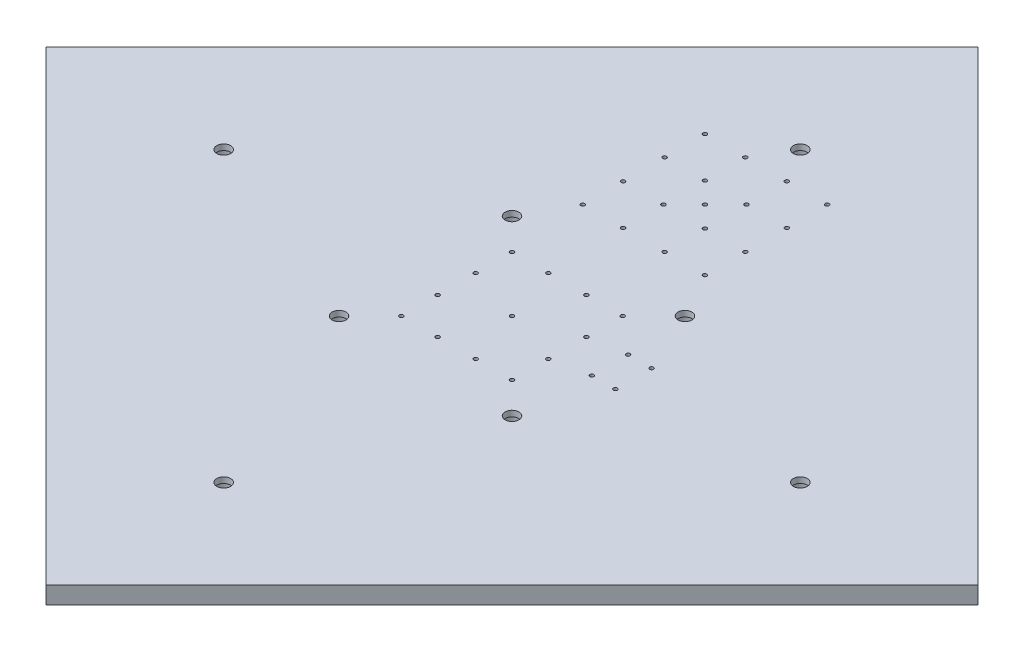
SolidWorks part; units mm, degrees
ref_plane "Front Plane" through (0, 0, 0) normal (0, 0, 1) x (1, 0, 0)
ref_plane "Top Plane" through (0, 0, 0) normal (0, 1, 0) x (1, 0, 0)
ref_plane "Right Plane" through (0, 0, 0) normal (1, 0, 0) x (0, 0, -1)
sketch "Sketch1" plane through (0, 0, 0) normal (0, 1, 0) x (1, 0, 0)
  line L0 (-404.1115, 0) -> (0, 404.1115)
  line L5 (-404.1115, 0) -> (0, -404.1115)
  line L6 (0, 404.1115) -> (404.1115, 0)
  line L7 (0, -404.1115) -> (404.1115, 0)
  line L8 (-404.1115, 0) -> (404.1115, 0) construction
  line L9 (0, 404.1115) -> (0, -404.1115) construction
  point P1 (0, 0)
  dimension "D1" = 571.5
extrude "Boss-Extrude1" add sketch "Sketch1" along normal blind 15
sketch "Extrusion Hole locations" plane through (0, 0, 0) normal (0, 1, 0) x (1, 0, 0)
  line L1 (75, -75) -> (-75, -75) construction
  line L2 (75, -75) -> (75, 75) construction
  line L3 (75, 75) -> (-75, 75) construction
  line L4 (-75, -75) -> (-75, 75) construction
  line L5 (75, -75) -> (-75, 75) construction
  line L6 (75, 75) -> (-75, -75) construction
  point P3 (0, 250)
  point P14 (250, 0)
  point P15 (0, -250)
  point P16 (-250, 0)
  point P105 (75, 75)
  point P108 (-75, 75)
  point P111 (-75, -75)
  point P114 (75, -75)
  dimension "D1" = 150
  dimension "D2" = 250
  dimension "D4" = 4
hole_wizard "CBORE for M10 SHCS1" positions "Extrusion Hole locations" profile "Sketch3" counterbore size "M10" standard "ANSI Metric" end condition through all
sketch "Sketch3" plane through (75, 0, 75) normal (1, 0, 0) x (0, 0, -1)
  line L0 (0, 0) -> (0, 15)
  line L1 (0, 15) -> (6, 15)
  line L3 (6, 15) -> (6, 10)
  line L4 (6, 10) -> (9, 10)
  line L5 (9, 10) -> (9, 0)
  line L7 (9, 0) -> (0, 0)
  line L11 (0, -6.35) -> (0, 107.95) construction
  dimension "Thru Hole Dia." = 12
  dimension "Thru Hole Depth" = 15
  dimension "C'Bore Dia." = 18
  dimension "C'Bore Depth" = 10
hole_wizard "CBORE for M3 SHCS1" positions "Sketch6" profile "Sketch7" counterbore size "M3" standard "ANSI Metric"
sketch "Sketch6" plane through (0, 0, 0) normal (0, -1, 0) x (-1, 0, 0)
  point P0 (0, 0)
  point P1 (0, 0)
  point P2 (-48, -48)
  point P3 (-48, -48)
  point P4 (16.5, -48)
  point P5 (-16.5, -48)
  point P6 (-16.5, -48)
  point P7 (48, -48)
  point P8 (48, -16.5)
  point P9 (48, 16.5)
  point P10 (48, 48)
  point P11 (16.5, 48)
  point P12 (-16.5, 48)
  point P13 (-48, 48)
  point P14 (0, 0)
  point P15 (0, 0)
  point P16 (-79.35, -10.1)
  point P17 (-99.7, -10.1)
  point P18 (-99.7, 21.3)
  point P19 (-79.35, 21.3)
  point P20 (-48, -16.5)
  point P21 (-48, 16.5)
sketch "Sketch7" plane through (0, 0, 0) normal (1, 0, 0) x (0, 0, -1)
  line L0 (0, 0) -> (0, 15)
  line L1 (0, 15) -> (1.7, 15)
  line L2 (1.7, 15) -> (1.7, 4)
  line L3 (1.7, 4) -> (3.25, 4)
  line L4 (3.25, 4) -> (3.25, 0)
  line L5 (3.25, 0) -> (0, 0)
  line L6 (0, -6.35) -> (0, 107.95) construction
  dimension "Thru Hole Dia." = 3.4
  dimension "Thru Hole Depth" = 15
  dimension "C'Bore Dia." = 6.5
  dimension "C'Bore Depth" = 4
hole_wizard "CBORE for M3 SHCS2" positions "Sketch8" profile "Sketch9" counterbore size "M3" standard "ANSI Metric"
sketch "Sketch8" plane through (0, 0, 0) normal (0, -1, 0) x (-1, 0, 0)
  point P0 (0, 167.3209)
  point P1 (0, 167.3209)
  point P2 (0, 167.3209)
  point P3 (53, 114.3209)
  point P4 (53, 149.3209)
  point P5 (53, 185.3209)
  point P6 (53, 220.3209)
  point P7 (18, 220.3209)
  point P8 (-18, 220.3209)
  point P9 (-53, 220.3209)
  point P10 (-53, 185.3209)
  point P11 (-53, 149.3209)
  point P12 (-53, 114.3209)
  point P13 (-18, 114.3209)
  point P14 (18, 114.3209)
  point P15 (18, 149.3209)
  point P16 (18, 185.3209)
  point P17 (-18, 149.3209)
  point P18 (-18, 185.3209)
sketch "Sketch9" plane through (0, 0, -167.3209) normal (1, 0, 0) x (0, 0, -1)
  line L0 (0, 0) -> (0, 15)
  line L1 (0, 15) -> (1.7, 15)
  line L2 (1.7, 15) -> (1.7, 4)
  line L3 (1.7, 4) -> (3.25, 4)
  line L4 (3.25, 4) -> (3.25, 0)
  line L5 (3.25, 0) -> (0, 0)
  line L6 (0, -6.35) -> (0, 107.95) construction
  dimension "Thru Hole Dia." = 3.4
  dimension "Thru Hole Depth" = 15
  dimension "C'Bore Dia." = 6.5
  dimension "C'Bore Depth" = 4
